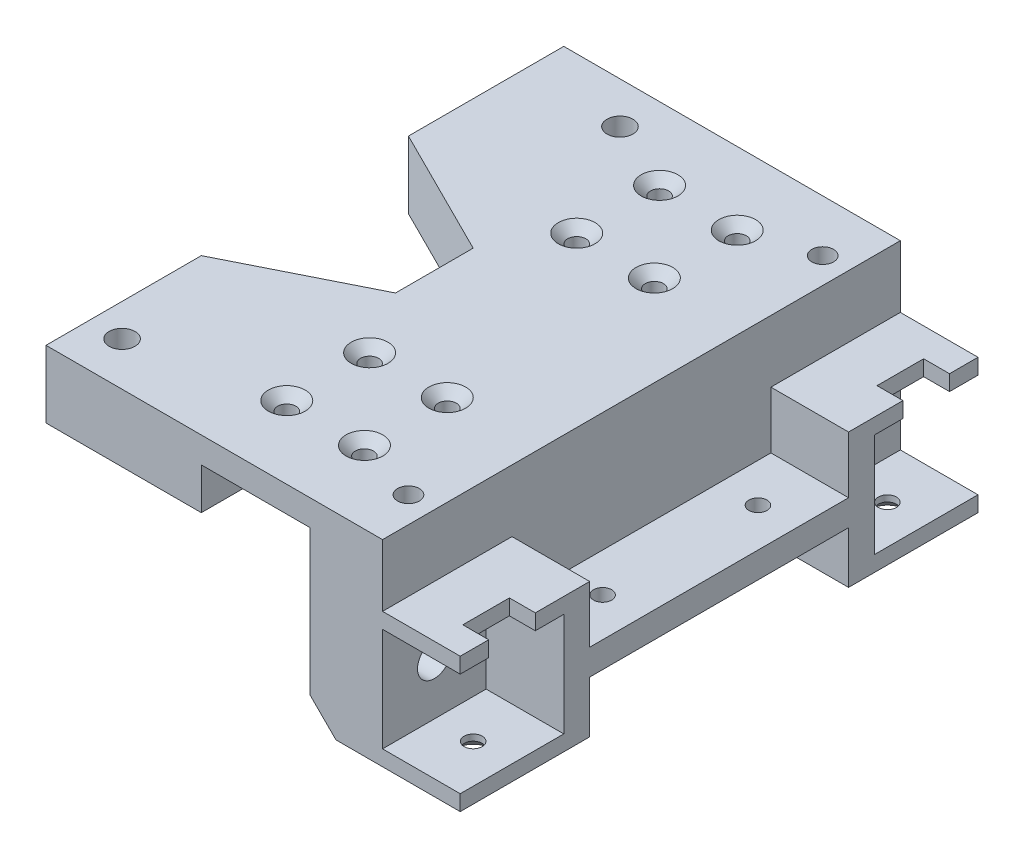
SolidWorks part; units mm, degrees
ref_plane "Front Plane" through (0, 0, 0) normal (0, 0, 1) x (1, 0, 0)
ref_plane "Top Plane" through (0, 0, 0) normal (0, 1, 0) x (1, 0, 0)
ref_plane "Right Plane" through (0, 0, 0) normal (1, 0, 0) x (0, 0, -1)
sketch "Sketch1" plane through (0, 0, 0) normal (0, 1, 0) x (1, 0, 0)
  line L0 (0, 50) -> (0, -50) construction
  line L1 (-10, 50) -> (10, 50)
  line L2 (-10, 50) -> (-10, -50)
  line L3 (-10, -50) -> (10, -50)
  line L4 (10, 50) -> (10, -50) construction
  line L5 (-10, 50) -> (10, -50) construction
  line L6 (-10, -50) -> (10, 50) construction
  line L7 (-7.5, 36) -> (7.5, 36) construction
  line L8 (-7.5, 36) -> (7.5, 20) construction
  line L9 (-10, 0) -> (10, 0) construction
  line L10 (-7.5, -36) -> (7.5, -20) construction
  line L11 (-7.5, -36) -> (7.5, -36) construction
  line L12 (-7.5, 20) -> (7.5, 20) construction
  line L13 (10, 50) -> (11, 50)
  line L14 (11, 50) -> (11, -50)
  line L15 (11, -50) -> (10, -50)
  circle A0 centre (-7.5, 36) radius 1.75
  circle A1 centre (7.5, 36) radius 1.75
  circle A2 centre (-7.5, 20) radius 1.75
  circle A3 centre (7.5, 20) radius 1.75
  circle A4 centre (7.5, -20) radius 1.75
  circle A5 centre (-7.5, -20) radius 1.75
  circle A6 centre (7.5, -36) radius 1.75
  circle A7 centre (-7.5, -36) radius 1.75
  point P0 (0, 0)
  point P16 (0, 36)
  dimension "D2" = 3.5
  dimension "D1" = 20
  dimension "D3" = 15
  dimension "D4" = 16
  dimension "D5" = 100
  dimension "D6" = 20
  dimension "D7" = 1
extrude "Boss-Extrude1" add sketch "Sketch1" along normal blind 5
sketch "Sketch2" plane through (11, 0, 0) normal (1, 0, 0) x (0, 0, -1)
  line L1 (-50, 5) -> (50, 5)
  line L2 (-50, 5) -> (-50, -33)
  line L3 (-50, -33) -> (50, -33)
  line L5 (50, 5) -> (50, -33)
  line L6 (50, 5) -> (50, 0) construction
  line L7 (-50, 5) -> (-50, 0) construction
  line L8 (-50, 5) -> (50, 5) construction
  dimension "D1" = 38
extrude "Boss-Extrude2" add sketch "Sketch2" along normal blind 14
sketch "Sketch3" plane through (25, 0, 0) normal (1, 0, 0) x (0, 0, -1)
  line L0 (0, 5) -> (0, -33) construction
  line L1 (-25, -18) -> (25, -18)
  line L2 (-25, -18) -> (-25, -23)
  line L3 (-25, -23) -> (25, -23)
  line L4 (25, -18) -> (25, -23)
  line L5 (50, 5) -> (-50, 5) construction
  line L6 (-50, -33) -> (50, -33) construction
  point P10 (0, -18)
  dimension "D1" = 5
  dimension "D2" = 50
  dimension "D3" = 10
extrude "Boss-Extrude3" add sketch "Sketch3" along normal blind 15
sketch "Sketch4" plane through (0, -18, 0) normal (0, 1, 0) x (1, 0, 0)
  line L0 (25, 0) -> (40, 0) construction
  line L1 (25, 25) -> (25, -25) construction
  line L2 (40, 25) -> (40, -25) construction
  line L3 (32.5, -15) -> (32.5, 15) construction
  circle A0 centre (32.5, 15) radius 1.75
  circle A1 centre (32.5, -15) radius 1.75
  point P8 (32.5, 0)
  dimension "D1" = 30
  dimension "D2" = 3.5
extrude "Cut-Extrude1" cut sketch "Sketch4" against normal through all
sketch "Sketch8" plane through (25, 0, 0) normal (1, 0, 0) x (0, 0, -1)
  line L0 (-50, 5) -> (-50, -33) construction
  line L1 (-50, -7) -> (-25, -7)
  line L2 (-50, -7) -> (-50, -10)
  line L3 (-50, -33) -> (-25, -33)
  line L4 (-25, -7) -> (-25, -33)
  line L5 (-50, -30) -> (-50, -33)
  line L6 (-50, -30) -> (-30, -30)
  line L8 (-50, -10) -> (-30, -10)
  line L9 (-30, -30) -> (-30, -10)
  line L10 (0, 20.9) -> (0, -20.9) construction
  line L11 (30, -30) -> (30, -10)
  line L12 (50, -10) -> (30, -10)
  line L13 (50, -30) -> (30, -30)
  line L14 (50, -30) -> (50, -33)
  line L15 (25, -7) -> (25, -33)
  line L16 (50, -33) -> (25, -33)
  line L17 (50, -7) -> (50, -10)
  line L18 (50, -7) -> (25, -7)
  line L19 (-50, -33) -> (50, -33) construction
  dimension "D1" = 3
  dimension "D2" = 5
  dimension "D3" = 3
  dimension "D4" = 20
  dimension "D5" = 20
extrude "Boss-Extrude6" add sketch "Sketch8" along normal blind 15
sketch "Sketch9" plane through (25, 0, 0) normal (1, 0, 0) x (0, 0, -1)
  line L0 (-50, -10) -> (-30, -30) construction
  line L1 (50, -10) -> (30, -30) construction
  circle A0 centre (-40, -20) radius 3.25
  circle A1 centre (40, -20) radius 3.25
  dimension "D1" = 6.5
extrude "Cut-Extrude3" cut sketch "Sketch9" against normal through all
sketch "Sketch10" plane through (11, 0, 0) normal (-1, 0, 0) x (0, 0, 1)
  circle A0 centre (-40, -20) radius 5.25
  circle A1 centre (40, -20) radius 5.25
  dimension "D1" = 10.5
extrude "Cut-Extrude4" cut sketch "Sketch10" against normal offset from surface (9 mm away) 5 up to face at (25, -20, 36.75)
sketch "Sketch11" plane through (0, -7, 0) normal (0, 1, 0) x (1, 0, 0)
  line L0 (40, -25) -> (40, -50) construction
  line L1 (40, -35.5) -> (35, -35.5)
  line L2 (40, -35.5) -> (40, -44.5)
  line L3 (40, -44.5) -> (35, -44.5)
  line L4 (35, -35.5) -> (35, -44.5)
  line L5 (35, -40) -> (40, -40) construction
  line L6 (40, -50) -> (25, -50) construction
  line L7 (-10, 0) -> (40, 0) construction
  line L8 (-10, 50) -> (-10, -50) construction
  line L9 (40, 25) -> (40, -25) construction
  line L10 (40, -35.5) -> (35, -35.5)
  line L11 (40, -44.5) -> (35, -44.5)
  line L12 (35, 40) -> (40, 40) construction
  line L13 (40, 44.5) -> (35, 44.5)
  line L14 (40, 35.5) -> (35, 35.5)
  line L15 (35, 35.5) -> (35, 44.5)
  line L16 (40, 44.5) -> (35, 44.5)
  line L17 (40, 35.5) -> (40, 44.5)
  line L18 (40, 35.5) -> (35, 35.5)
  line M7 (40, -50) -> (40, -25)
  dimension "D1" = 9
  dimension "D2" = 10
  dimension "D3" = 5
extrude "Cut-Extrude5" cut sketch "Sketch11" against normal up to next contours L1 L4 L3 M7 | L14 L17 L13 L15 region at (37.5, -7, 40) region at (37.5, -7, -40)
sketch "Sketch12" plane through (0, -30, 0) normal (0, 1, 0) x (1, 0, 0)
  line L0 (40, -40) -> (25, -40) construction
  line L1 (40, -30) -> (40, -50) construction
  line L2 (25, -25) -> (25, -50) construction
  line L3 (-20.9, 0) -> (20.9, 0) construction
  circle A0 centre (32.5, -40) radius 1.75
  circle A2 centre (32.5, 40) radius 1.75
  dimension "D1" = 3.5
extrude "Cut-Extrude6" cut sketch "Sketch12" against normal through all
sketch "Sketch13" plane through (-10, 0, 0) normal (-1, 0, 0) x (0, 0, 1)
  line L1 (-50, 5) -> (50, 5)
  line L2 (-50, 5) -> (-50, -8)
  line L3 (-50, -8) -> (50, -8)
  line L4 (50, 5) -> (50, -8)
  dimension "D1" = 13
extrude "Boss-Extrude7" add sketch "Sketch13" along normal blind 30
sketch "Sketch14" plane through (0, 5, 0) normal (0, 1, 0) x (1, 0, 0)
  line L6 (-27.65, 42) -> (-27.65, -41.58) construction
  line L12 (-21.15, 35.5) -> (40, 35.5) construction
  line L18 (-33.73, -35.5) -> (40, -35.5) construction
  circle A0 centre (-21.15, 42) radius 2.5
  circle A1 centre (-33.73, -41.58) radius 2.5
  circle A2 centre (-33.73, -41.58) radius 6.08 construction
  circle A3 centre (-21.15, 42) radius 6.5 construction
  dimension "D1" = 5
  dimension "D2" = 5
  dimension "D4" = 12.16
  dimension "D5" = 13
  dimension "D3" = 21.15
extrude "Cut-Extrude7" cut sketch "Sketch14" against normal through all
sketch "Sketch15" plane through (0, -8, 0) normal (0, -1, 0) x (1, 0, 0)
  line L0 (-40, -50) -> (-40, 50) construction
  line L1 (-29.63, 43.9471) -> (-33.73, 46.3143)
  line L2 (-33.73, 46.3143) -> (-37.83, 43.9471)
  line L3 (-37.83, 43.9471) -> (-37.83, 39.2129)
  line L4 (-37.83, 39.2129) -> (-33.73, 36.8457)
  line L5 (-33.73, 36.8457) -> (-29.63, 39.2129)
  line L6 (-29.63, 39.2129) -> (-29.63, 43.9471)
  line L7 (-17.05, -44.3671) -> (-17.05, -39.6329)
  line L8 (-17.05, -39.6329) -> (-21.15, -37.2657)
  line L9 (-21.15, -37.2657) -> (-25.25, -39.6329)
  line L10 (-25.25, -39.6329) -> (-25.25, -44.3671)
  line L11 (-25.25, -44.3671) -> (-21.15, -46.7343)
  line L12 (-21.15, -46.7343) -> (-17.05, -44.3671)
  circle A0 centre (-33.73, 41.58) radius 4.1 construction
  circle A1 centre (-21.15, -42) radius 4.1 construction
  dimension "D1" = 8.2
extrude "Cut-Extrude8" cut sketch "Sketch15" against normal blind 5
sketch "Sketch16" plane through (0, 5, 0) normal (0, 1, 0) x (1, 0, 0)
  line L0 (20, 40) -> (40, 40) construction
  line L1 (40, 40) -> (40, -40) construction
  line L2 (40, -40) -> (20, -40) construction
  line L3 (20, -40) -> (20, 40) construction
  line L4 (40, 50) -> (40, 30) construction
  line L5 (40, -30) -> (40, -50) construction
  circle A0 centre (20, 40) radius 2.1
  circle A1 centre (20, -40) radius 2.1
  dimension "D1" = 4.2
  dimension "D2" = 4.2
  dimension "D3" = 20
extrude "Cut-Extrude9" cut sketch "Sketch16" against normal blind 4
chamfer "Chamfer1" distance 1.8 angle 45 8 edges at (7.5, 5, 34.25) (-7.5, 5, 34.25) (7.5, 5, 18.25) (-7.5, 5, 18.25) (7.5, 5, -18.25) (-7.5, 5, -18.25) (7.5, 5, -34.25) (-7.5, 5, -34.25)
sketch "Sketch17" plane through (0, 5, 0) normal (0, 1, 0) x (1, 0, 0)
  line L0 (-40, 20) -> (-15, 7.5)
  line L1 (-40, -50) -> (-40, 50) construction
  line L2 (-15, 7.5) -> (-15, -7.5)
  line L3 (-15, -7.5) -> (-40, -20)
  line L4 (-40, -20) -> (-40, 20)
  point P5 (-15, 0)
  dimension "D1" = 15
  dimension "D2" = 25
  dimension "D3" = 40
extrude "Cut-Extrude10" cut sketch "Sketch17" against normal through all
chamfer "Chamfer2" distance 1.8 angle 45 2 edges at (32.5, -33, -41.75) (32.5, -33, 41.75)
chamfer "Chamfer3" distance 5 angle 45 1 edges at (11, -33, 0)
